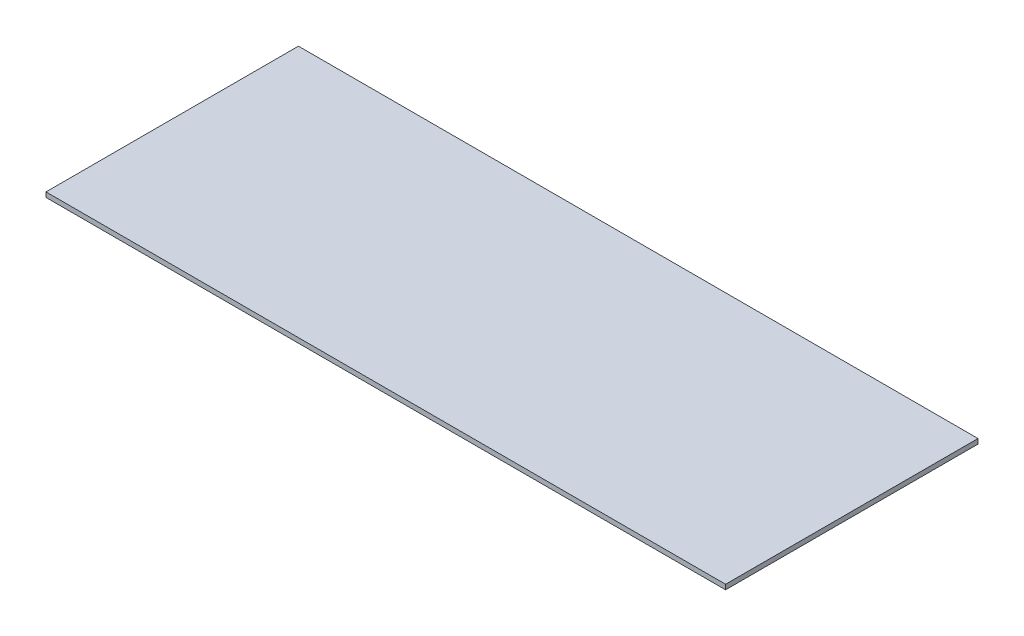
SolidWorks part; units mm, degrees
material "Acrylic (Medium-high impact)"
ref_plane "Front" through (0, 0, 0) normal (0, 0, 1) x (1, 0, 0)
ref_plane "Top" through (0, 0, 0) normal (0, 1, 0) x (1, 0, 0)
ref_plane "Right" through (0, 0, 0) normal (1, 0, 0) x (0, 0, -1)
sketch "Sketch1" plane through (0, 0, 0) normal (0, 1, 0) x (1, 0, 0)
  line L1 (-222.25, -82.55) -> (222.25, -82.55)
  line L2 (-222.25, -82.55) -> (-222.25, 82.55)
  line L3 (-222.25, 82.55) -> (222.25, 82.55)
  line L4 (222.25, -82.55) -> (222.25, 82.55)
  line L5 (-222.25, -82.55) -> (222.25, 82.55) construction
  line L6 (-222.25, 82.55) -> (222.25, -82.55) construction
  point P0 (0, 0)
  dimension "D1" = 165.1
  dimension "D2" = 444.5
extrude "Boss-Extrude1" add sketch "Sketch1" along normal blind 3.175
